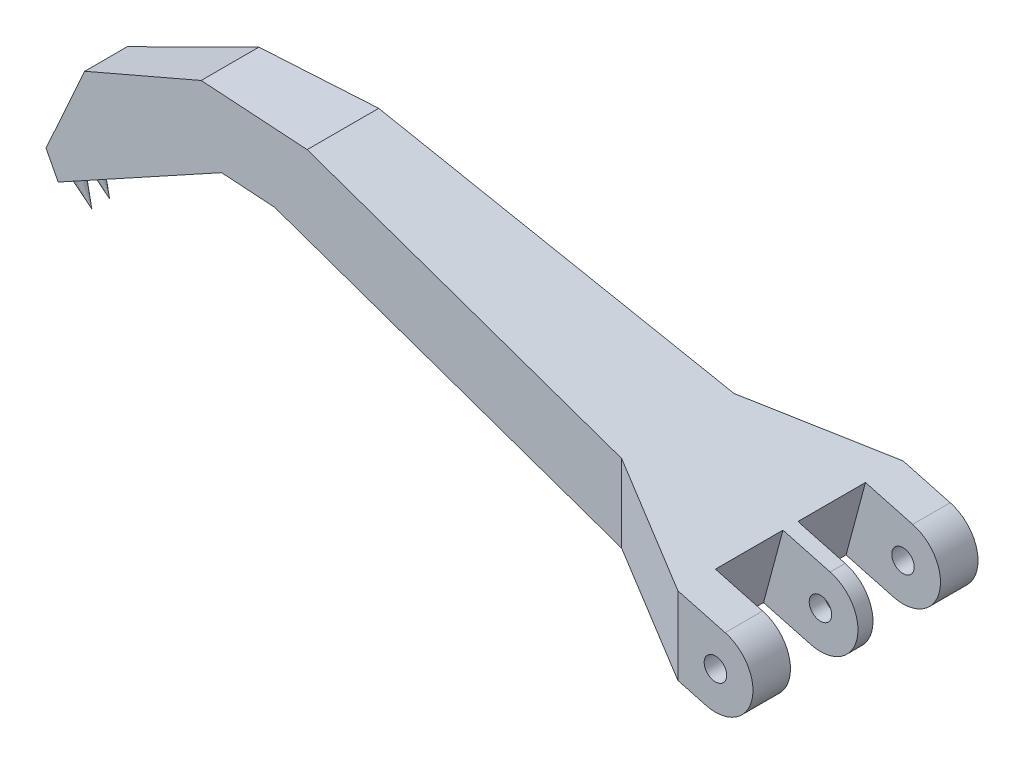
SolidWorks part; units mm, degrees
ref_plane "Front Plane" through (0, 0, 0) normal (0, 0, 1) x (1, 0, 0)
ref_plane "Top Plane" through (0, 0, 0) normal (0, 1, 0) x (1, 0, 0)
ref_plane "Right Plane" through (0, 0, 0) normal (1, 0, 0) x (0, 0, -1)
sketch "Sketch3" plane through (0, 0, 0) normal (0, 0, 1) x (1, 0, 0)
  line L0 (1.2941, 4.8296) -> (-64.6526, 22.5)
  line L1 (-64.6526, 22.5) -> (-79.7011, 22.5)
  line L2 (-79.7011, 22.5) -> (-96.234, 14.7906)
  line L3 (-96.234, 14.7906) -> (-101.7321, 3)
  line L4 (-101.7321, 3) -> (-100, 0)
  line L5 (-100, 0) -> (-76.8063, 13.3909)
  line L6 (-76.8063, 13.3909) -> (-69.2941, 13.3909)
  line L7 (-69.2941, 13.3909) -> (-1.2941, -4.8296)
  line L8 (-1.2941, -4.8296) -> (1.2941, 4.8296) construction
  line L9 (-5.9592, -3.5796) -> (-3.371, 6.0796) construction
  line L10 (-100, 0) -> (0, 0) construction
  circle A0 centre (0, 0) radius 1.5
  arc A2 (-1.2941, -4.8296) -> (1.2941, 4.8296) centre (0, 0) ccw
  point P7 (0, 0)
  point P14 (-5, 0)
  point P15 (0, 0)
  point P16 (0, 0)
  dimension "D2" = 3
  dimension "D1" = 100
  dimension "D3" = 10
  dimension "D4" = 68
  dimension "D5" = 30
  dimension "D6" = 15
  dimension "D7" = 125
  dimension "D8" = 5.498
  dimension "D9" = 3
  dimension "D10" = 155
  dimension "D11" = 22.5
sketch "Sketch4" plane through (0, 0, 0) normal (1, 0, 0) x (0, 0, -1)
  line L0 (-15, 0) -> (15, 0)
  point P4 (0, 0)
  dimension "D1" = 30
ref_plane "Plane1" through (-101.7321, 0, 0) normal (1, 0, 0) x (0, 0, -1)
sketch "Sketch5" plane through (-101.7321, 0, 0) normal (1, 0, 0) x (0, 0, -1)
  line L0 (2.5, 0) -> (-2.5, 0)
  point P4 (0, 0)
  dimension "D1" = 5
sketch "Sketch14" plane through (0, 0, 0) normal (0, 0, 1) x (1, 0, 0)
  line L0 (-153.9208, -162.5929) -> (-22.7793, -162.5929) construction
extrude "Boss-Extrude2" add sketch "Sketch3" along direction (0, 0, -1) on the side against the normal up to vertex (15 mm away) and the other way up to vertex (15 mm away) up to point (0, 0, -15) other way up to point (0, 0, 15)
sketch "Sketch12" plane through (0, 0, 0) normal (0, 1, 0) x (1, 0, 0)
  line L0 (-101.7321, 2.5) -> (-101.7321, -2.5) construction
  line L1 (-101.7321, 2.5) -> (-5, 2.5) construction
  line L2 (-101.7321, 2.5) -> (-101.7321, -2.5)
  line L3 (-5, -15) -> (-5, 15)
  line L4 (-101.7321, 2.5) -> (-5, 15) construction
  line L5 (-101.7321, -2.5) -> (-5, -15) construction
  line L6 (-101.7321, 0) -> (0, 0) construction
  line L7 (0, -15) -> (0, 15) construction
  line L8 (0, -15) -> (0, 15) construction
  line L9 (-101.7321, 2.5) -> (-20, 7.5)
  line L10 (-20, 7.5) -> (-5, 15)
  line L11 (-20, -7.5) -> (-5, -15)
  line L12 (-101.7321, -2.5) -> (-20, -7.5)
  point P9 (0, 0)
  point P12 (0, 0)
  point P13 (0, 0)
  dimension "D1" = 5
  dimension "D2" = 7.5
  dimension "D3" = 15
extrude "Cut-Extrude2" cut sketch "Sketch12" along normal through all and the other way through all flip side to cut contours L2 L12 L11 L3 L10 L9 | L3 L10 L9 L2 L12 L11 region at (-41.6669, 0, 0)
sketch "Sketch13" plane through (0, 0, 0) normal (0, 0, 1) x (1, 0, 0)
  line L0 (-5, 6.5161) -> (-5, -3.8366) construction
  line L1 (-5, 6.5161) -> (-5, -3.8366)
  line L8 (1.2941, 4.8296) -> (-5, 6.5161)
  line L9 (-1.2941, -4.8296) -> (-5, -3.8366)
  arc A0 (-1.2941, -4.8296) -> (1.2941, 4.8296) centre (0, 0) ccw construction
  circle A1 centre (0, 0) radius 1.5 construction
  arc A2 (-1.2941, -4.8296) -> (1.2941, 4.8296) centre (0, 0) ccw
  circle A3 centre (0, 0) radius 1.5
extrude "Boss-Extrude3" add sketch "Sketch13" along direction (0, 0, 1) on the side of the normal up to vertex (15 mm away) and the other way up to vertex (15 mm away) up to point (-5, 6.5161, 15) other way up to point (-5, 6.5161, -15)
sketch "Sketch16" plane through (1.2941, 4.8296, 0) normal (0.2588, 0.9659, 0) x (0.9659, -0.2588, 0)
  line L0 (5, -15) -> (5, 15) construction
  line L1 (5, -15) -> (5, 15) construction
  line L2 (5, 15) -> (0, 15) construction
  line L3 (0, -15) -> (5, -15) construction
  line L4 (5, 15) -> (0, 15) construction
  line L5 (0, -15) -> (5, -15) construction
  line L6 (0, 15) -> (-6.5161, 15) construction
  line L7 (0, -15) -> (-6.5161, -15) construction
  line L8 (0, 15) -> (-6.5161, 15) construction
  line L9 (0, -15) -> (-6.5161, -15) construction
  line L10 (-6.5161, -15) -> (-6.5161, 15) construction
  line L11 (5, 0) -> (-6.5161, 0) construction
  line L12 (5, -1) -> (-6.5161, -1)
  line L13 (-6.5161, 1) -> (5, 1)
  line L14 (-6.5161, -10) -> (5, -10)
  line L15 (-6.5161, 10) -> (5, 10)
  line L16 (5, -10) -> (-6.5161, -10)
  line L17 (-6.5161, -10) -> (-6.5161, -1)
  line L18 (5, -1) -> (5, -10)
  line L19 (-6.5161, 10) -> (-6.5161, 1)
  line L20 (5, 1) -> (5, 10)
  line L21 (5, -1) -> (5, -10)
  line L22 (-6.5161, -10) -> (-6.5161, -1)
  line M12 (0, -15) -> (0, 15)
  dimension "D1" = 2
  dimension "D2" = 9
extrude "Cut-Extrude8" cut sketch "Sketch16" against normal up to surface (10 mm away) contours L15 L19 L13 M12 | L17 L14 L12 M12 | L18 L12 L14 M12 | L13 L20 L15 M12 region at (3.7089, 4.1826, 5.5) region at (-1.853, 5.6729, -5.5) region at (3.7089, 4.1826, -5.5) region at (-1.853, 5.6729, 5.5) up to face at (-23.897, 1.2268, 0)
sketch "Sketch17" plane through (-25, 43.3013, 0) normal (0.5, -0.866, 0) x (0.866, 0.5, 0)
  line L0 (-86.6025, 0) -> (-59.8207, 0) construction
  line L1 (-86.6025, -2.606) -> (-86.6025, 2.606) construction
  line L2 (-59.8207, -4.0248) -> (-59.8207, 4.0248) construction
  line L3 (-86.6025, 2.606) -> (-59.8207, 4.0248) construction
  circle A0 centre (-85.1025, 1.1833) radius 0.75
  circle A1 centre (-85.1025, -1.1833) radius 0.75
  dimension "D1" = 1.5
  dimension "D2" = 1.5
  dimension "D3" = 1.5
extrude "Boss-Extrude4" add sketch "Sketch17" along normal blind 6 draft 12
